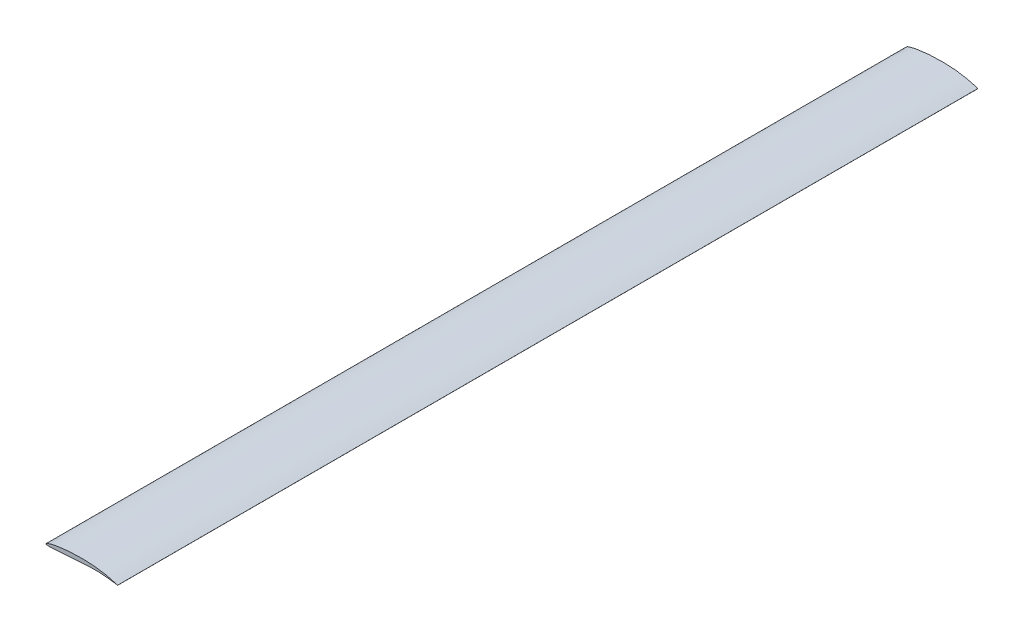
SolidWorks part; units mm, degrees
ref_plane "Front Plane" through (0, 0, 0) normal (0, 0, 1) x (1, 0, 0)
ref_plane "Top Plane" through (0, 0, 0) normal (0, 1, 0) x (1, 0, 0)
ref_plane "Right Plane" through (0, 0, 0) normal (1, 0, 0) x (0, 0, -1)
curve "Curve1"
  spline degree 3 poles (25.4, 0.016, 0) (25.3391, 0.0354, 0) (25.1691, 0.0896, 0) (24.8604, 0.1853, 0) (24.4521, 0.3079, 0) (23.9748, 0.4451, 0) (23.4435, 0.5905, 0) (22.8682, 0.7391, 0) (22.2564, 0.887, 0) (21.6142, 1.0313, 0) (20.9466, 1.1694, 0) (20.258, 1.299, 0) (19.5521, 1.4184, 0) (18.8325, 1.5262, 0) (18.1021, 1.6212, 0) (17.3637, 1.7024, 0) (16.6199, 1.7689, 0) (15.8731, 1.8208, 0) (15.1255, 1.8558, 0) (14.3793, 1.8809, 0) (13.6365, 1.8983, 0) (12.8989, 1.9074, 0) (12.1682, 1.9083, 0) (11.4461, 1.901, 0) (10.7342, 1.8857, 0) (10.0342, 1.8625, 0) (9.3474, 1.8315, 0) (8.6753, 1.7932, 0) (8.0194, 1.7478, 0) (7.3808, 1.6956, 0) (6.761, 1.637, 0) (6.1612, 1.5726, 0) (5.5826, 1.5027, 0) (5.0264, 1.428, 0) (4.4936, 1.3489, 0) (3.9856, 1.2661, 0) (3.5033, 1.1802, 0) (3.0477, 1.0919, 0) (2.6201, 1.0017, 0) (2.2213, 0.9105, 0) (1.8523, 0.8188, 0) (1.5142, 0.7273, 0) (1.2078, 0.6366, 0) (0.9341, 0.5475, 0) (0.694, 0.4605, 0) (0.4882, 0.3763, 0) (0.3176, 0.2954, 0) (0.1826, 0.2183, 0) (0.0836, 0.145, 0) (0.0195, 0.0755, 0) (-0.008, 0.0023, 0) (0.0173, -0.0678, 0) (0.0849, -0.1179, 0) (0.1842, -0.1582, 0) (0.3194, -0.1909, 0) (0.4898, -0.2162, 0) (0.6954, -0.2344, 0) (0.9354, -0.2455, 0) (1.209, -0.2497, 0) (1.5153, -0.2472, 0) (1.8533, -0.2383, 0) (2.2222, -0.2234, 0) (2.621, -0.2028, 0) (3.0486, -0.1768, 0) (3.504, -0.1458, 0) (3.9863, -0.1104, 0) (4.4943, -0.0708, 0) (5.0269, -0.0277, 0) (5.5831, 0.0186, 0) (6.1617, 0.0673, 0) (6.7614, 0.1181, 0) (7.3812, 0.1704, 0) (8.0196, 0.2236, 0) (8.6755, 0.2771, 0) (9.3475, 0.3304, 0) (10.0343, 0.3829, 0) (10.7343, 0.4341, 0) (11.446, 0.4835, 0) (12.1681, 0.5305, 0) (12.8988, 0.5746, 0) (13.6364, 0.6156, 0) (14.3791, 0.6529, 0) (15.1252, 0.6867, 0) (15.8725, 0.7144, 0) (16.6192, 0.7287, 0) (17.363, 0.7312, 0) (18.1013, 0.7217, 0) (18.8317, 0.7006, 0) (19.5514, 0.6682, 0) (20.2572, 0.6255, 0) (20.9458, 0.5732, 0) (21.6134, 0.5125, 0) (22.2557, 0.4449, 0) (22.8675, 0.3721, 0) (23.4429, 0.2962, 0) (23.9743, 0.2197, 0) (24.4517, 0.1457, 0) (24.8601, 0.0785, 0) (25.1689, 0.0253, 0) (25.3391, -0.0051, 0) (25.4, -0.016, 0) knots 0 0 0 0 0.003729 0.010403 0.018841 0.028586 0.039358 0.050957 0.063231 0.076057 0.089334 0.102977 0.11691 0.131071 0.145402 0.159854 0.17438 0.18894 0.203496 0.218017 0.232469 0.246817 0.261029 0.275074 0.288921 0.302543 0.315913 0.329004 0.341791 0.35425 0.366358 0.37809 0.389424 0.400339 0.410813 0.420824 0.430352 0.439376 0.447877 0.455834 0.463229 0.470043 0.476257 0.481856 0.486823 0.491146 0.494814 0.497827 0.500195 0.50197 0.5033 0.504509 0.506013 0.508063 0.510747 0.514093 0.518105 0.522777 0.528099 0.534057 0.540634 0.547815 0.555582 0.563914 0.572793 0.582198 0.592109 0.602502 0.613357 0.624649 0.636356 0.648452 0.660912 0.673711 0.686822 0.700217 0.713868 0.727745 0.741819 0.756057 0.770426 0.784892 0.799419 0.813968 0.828496 0.842964 0.85733 0.871548 0.885567 0.89933 0.912776 0.925832 0.938415 0.950429 0.961757 0.972255 0.981732 0.989922 0.99639 1 1 1 1
sketch "Sketch3" plane through (0, 0, 0) normal (0, 0, 1) x (1, 0, 0)
  line L0 (25.4, 0.016) -> (25.4, -0.016)
  line L1 (0, 0) -> (25.4, 0) construction
  spline S0 degree 3 poles (669.244, 1893.2813) (49.9556, -17.1731) (38.8562, -4.1548) (24.8604, 0.1853) (24.4521, 0.3079) (23.7837, 0.5001) (22.615, 0.8106) (21.3697, 1.0897) (20.0193, 1.3439) (19.0695, 1.4954) (18.1021, 1.6212) (17.3637, 1.7024) (16.6199, 1.7689) (15.8731, 1.8208) (15.1255, 1.8558) (14.3793, 1.8809) (13.6365, 1.8983) (12.658, 1.9103) (11.6898, 1.9063) (10.505, 1.8807) (9.5807, 1.8449) (8.6753, 1.7932) (8.0194, 1.7478) (7.3808, 1.6956) (6.761, 1.637) (6.1612, 1.5726) (5.5826, 1.5027) (5.0264, 1.428) (4.4936, 1.3489) (3.9856, 1.2661) (3.5033, 1.1802) (3.0477, 1.0919) (2.6201, 1.0017) (2.2213, 0.9105) (1.8523, 0.8188) (1.5142, 0.7273) (1.2078, 0.6366) (0.9341, 0.5475) (0.694, 0.4605) (0.4882, 0.3763) (0.3176, 0.2954) (0.1826, 0.2183) (0.0836, 0.145) (0.0195, 0.0755) (-0.008, 0.0023) (0.0173, -0.0678) (0.0849, -0.1179) (0.1842, -0.1582) (0.3194, -0.1909) (0.4898, -0.2162) (0.6954, -0.2344) (0.9354, -0.2455) (1.209, -0.2497) (1.5153, -0.2472) (1.8533, -0.2383) (2.2222, -0.2234) (2.621, -0.2028) (3.0486, -0.1768) (3.504, -0.1458) (3.9863, -0.1104) (4.4943, -0.0708) (5.0269, -0.0277) (5.5831, 0.0186) (6.1617, 0.0673) (6.7614, 0.1181) (7.3812, 0.1704) (8.0196, 0.2236) (8.6755, 0.2771) (9.5809, 0.3489) (10.7458, 0.4363) (11.9305, 0.5161) (12.8988, 0.5746) (13.6364, 0.6156) (14.3791, 0.6529) (15.1252, 0.6867) (15.8725, 0.7144) (16.6192, 0.7287) (17.363, 0.7312) (18.1013, 0.7217) (19.0677, 0.6937) (20.2411, 0.6319) (21.5894, 0.5195) (22.6536, 0.4003) (23.4429, 0.2962) (23.9743, 0.2197) (24.4517, 0.1457) (24.8601, 0.0785) (40.0053, -2.5297) (53.5468, -13.3976) (418.1188, 1960.8142) knots -0.835522 -0.835522 -0.835522 -0.835522 0.003729 0.010403 0.018841 0.028586 0.050957 0.089334 0.102977 0.131071 0.145402 0.159854 0.17438 0.18894 0.203496 0.218017 0.232469 0.246817 0.275074 0.288921 0.315913 0.329004 0.341791 0.35425 0.366358 0.37809 0.389424 0.400339 0.410813 0.420824 0.430352 0.439376 0.447877 0.455834 0.463229 0.470043 0.476257 0.481856 0.486823 0.491146 0.494814 0.497827 0.500195 0.50197 0.5033 0.504509 0.506013 0.508063 0.510747 0.514093 0.518105 0.522777 0.528099 0.534057 0.540634 0.547815 0.555582 0.563914 0.572793 0.582198 0.592109 0.602502 0.613357 0.624649 0.636356 0.648452 0.660912 0.673711 0.686822 0.713868 0.741819 0.756057 0.770426 0.784892 0.799419 0.813968 0.828496 0.842964 0.85733 0.871548 0.89933 0.925832 0.950429 0.961757 0.972255 0.981732 0.989922 0.99639 1.877782 1.877782 1.877782 1.877782 only from (25.4, 0.016) to (25.4, -0.016) construction
  spline S1 degree 3 poles (25.4, 0.016) (25.3391, 0.0354) (25.1691, 0.0896) (24.8604, 0.1853) (24.4521, 0.3079) (23.7837, 0.5001) (22.615, 0.8106) (21.3697, 1.0897) (20.0193, 1.3439) (19.0695, 1.4954) (18.1021, 1.6212) (17.3637, 1.7024) (16.6199, 1.7689) (15.8731, 1.8208) (15.1255, 1.8558) (14.3793, 1.8809) (13.6365, 1.8983) (12.658, 1.9103) (11.6898, 1.9063) (10.505, 1.8807) (9.5807, 1.8449) (8.6753, 1.7932) (8.0194, 1.7478) (7.3808, 1.6956) (6.761, 1.637) (6.1612, 1.5726) (5.5826, 1.5027) (5.0264, 1.428) (4.4936, 1.3489) (3.9856, 1.2661) (3.5033, 1.1802) (3.0477, 1.0919) (2.6201, 1.0017) (2.2213, 0.9105) (1.8523, 0.8188) (1.5142, 0.7273) (1.2078, 0.6366) (0.9341, 0.5475) (0.694, 0.4605) (0.4882, 0.3763) (0.3176, 0.2954) (0.1826, 0.2183) (0.0836, 0.145) (0.0195, 0.0755) (-0.008, 0.0023) (0.0173, -0.0678) (0.0849, -0.1179) (0.1842, -0.1582) (0.3194, -0.1909) (0.4898, -0.2162) (0.6954, -0.2344) (0.9354, -0.2455) (1.209, -0.2497) (1.5153, -0.2472) (1.8533, -0.2383) (2.2222, -0.2234) (2.621, -0.2028) (3.0486, -0.1768) (3.504, -0.1458) (3.9863, -0.1104) (4.4943, -0.0708) (5.0269, -0.0277) (5.5831, 0.0186) (6.1617, 0.0673) (6.7614, 0.1181) (7.3812, 0.1704) (8.0196, 0.2236) (8.6755, 0.2771) (9.5809, 0.3489) (10.7458, 0.4363) (11.9305, 0.5161) (12.8988, 0.5746) (13.6364, 0.6156) (14.3791, 0.6529) (15.1252, 0.6867) (15.8725, 0.7144) (16.6192, 0.7287) (17.363, 0.7312) (18.1013, 0.7217) (19.0677, 0.6937) (20.2411, 0.6319) (21.5894, 0.5195) (22.6536, 0.4003) (23.4429, 0.2962) (23.9743, 0.2197) (24.4517, 0.1457) (24.8601, 0.0785) (25.1689, 0.0253) (25.3391, -0.0051) (25.4, -0.016) knots 0 0 0 0 0.003729 0.010403 0.018841 0.028586 0.050957 0.089334 0.102977 0.131071 0.145402 0.159854 0.17438 0.18894 0.203496 0.218017 0.232469 0.246817 0.275074 0.288921 0.315913 0.329004 0.341791 0.35425 0.366358 0.37809 0.389424 0.400339 0.410813 0.420824 0.430352 0.439376 0.447877 0.455834 0.463229 0.470043 0.476257 0.481856 0.486823 0.491146 0.494814 0.497827 0.500195 0.50197 0.5033 0.504509 0.506013 0.508063 0.510747 0.514093 0.518105 0.522777 0.528099 0.534057 0.540634 0.547815 0.555582 0.563914 0.572793 0.582198 0.592109 0.602502 0.613357 0.624649 0.636356 0.648452 0.660912 0.673711 0.686822 0.713868 0.741819 0.756057 0.770426 0.784892 0.799419 0.813968 0.828496 0.842964 0.85733 0.871548 0.89933 0.925832 0.950429 0.961757 0.972255 0.981732 0.989922 0.99639 1 1 1 1
sketch "Sketch4" plane through (0, 0, 0) normal (0, 0, 1) x (1, 0, 0)
  line L0 (132.08, 0.0832) -> (132.08, -0.0832)
  spline S1 degree 3 poles (132.08, 0.0832) (131.7631, 0.1842) (130.8791, 0.4658) (129.2742, 0.9635) (127.151, 1.6009) (123.675, 2.6006) (117.5982, 4.2151) (111.1222, 5.6666) (104.1002, 6.9884) (99.1613, 7.7762) (94.1307, 8.4302) (90.2911, 8.8523) (86.4235, 9.1984) (82.5403, 9.468) (78.6526, 9.6503) (74.7726, 9.7804) (70.91, 9.8711) (65.8217, 9.9337) (60.7868, 9.9125) (54.6259, 9.7799) (49.8194, 9.5932) (45.1118, 9.3247) (41.7008, 9.0884) (38.3804, 8.8169) (35.1574, 8.5124) (32.0383, 8.1773) (29.0295, 7.814) (26.137, 7.4254) (23.3669, 7.0142) (20.725, 6.5838) (18.2169, 6.1372) (15.8482, 5.6778) (13.6244, 5.2091) (11.5506, 4.7345) (9.632, 4.2575) (7.8737, 3.7817) (6.2806, 3.3104) (4.8573, 2.8471) (3.6086, 2.3948) (2.5386, 1.9569) (1.6514, 1.536) (0.9496, 1.1354) (0.4347, 0.754) (0.1014, 0.3927) (-0.0418, 0.012) (0.0898, -0.3524) (0.4416, -0.6132) (0.9579, -0.8229) (1.6607, -0.9926) (2.547, -1.1245) (3.6163, -1.2189) (4.8643, -1.2765) (6.2869, -1.2983) (7.8795, -1.2854) (9.6374, -1.2394) (11.5556, -1.1619) (13.629, -1.0545) (15.8525, -0.9193) (18.2209, -0.7583) (20.7286, -0.5739) (23.3702, -0.3682) (26.14, -0.1439) (29.0322, 0.0965) (32.0407, 0.3502) (35.1594, 0.6144) (38.3821, 0.8862) (41.7021, 1.1627) (45.1128, 1.441) (49.8208, 1.8144) (55.878, 2.2686) (62.0387, 2.6837) (67.0735, 2.9881) (70.9091, 3.2013) (74.7715, 3.395) (78.6508, 3.571) (82.537, 3.7148) (86.42, 3.789) (90.2874, 3.8023) (94.1268, 3.7528) (99.1519, 3.6074) (105.2535, 3.2859) (112.265, 2.7016) (117.7985, 2.0818) (121.9032, 1.5402) (124.6665, 1.1422) (127.1488, 0.7577) (129.2727, 0.408) (130.8783, 0.1315) (131.7631, -0.0266) (132.08, -0.0832) knots 0 0 0 0 0.003729 0.010403 0.018841 0.028586 0.050957 0.089334 0.102977 0.131071 0.145402 0.159854 0.17438 0.18894 0.203496 0.218017 0.232469 0.246817 0.275074 0.288921 0.315913 0.329004 0.341791 0.35425 0.366358 0.37809 0.389424 0.400339 0.410813 0.420824 0.430352 0.439376 0.447877 0.455834 0.463229 0.470043 0.476257 0.481856 0.486823 0.491146 0.494814 0.497827 0.500195 0.50197 0.5033 0.504509 0.506013 0.508063 0.510747 0.514093 0.518105 0.522777 0.528099 0.534057 0.540634 0.547815 0.555582 0.563914 0.572793 0.582198 0.592109 0.602502 0.613357 0.624649 0.636356 0.648452 0.660912 0.673711 0.686822 0.713868 0.741819 0.756057 0.770426 0.784892 0.799419 0.813968 0.828496 0.842964 0.85733 0.871548 0.89933 0.925832 0.950429 0.961757 0.972255 0.981732 0.989922 0.99639 1 1 1 1
extrude "Boss-Extrude1" add sketch "Sketch4" along normal blind 1584.96
